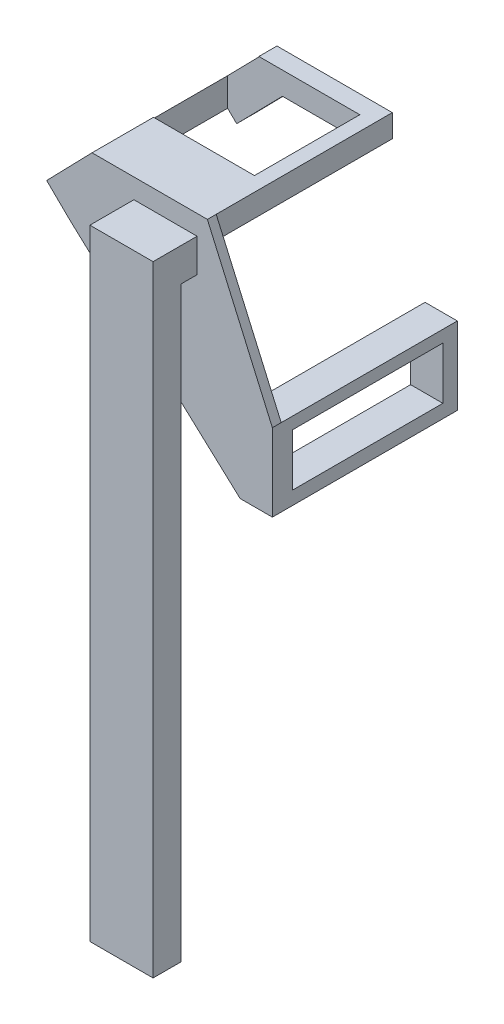
SolidWorks part; units mm, degrees
ref_plane "Front Plane" through (0, 0, 0) normal (0, 0, 1) x (1, 0, 0)
ref_plane "Top Plane" through (0, 0, 0) normal (0, 1, 0) x (1, 0, 0)
ref_plane "Right Plane" through (0, 0, 0) normal (1, 0, 0) x (0, 0, -1)
sketch "Sketch1" plane through (0, 0, 0) normal (0, 0, 1) x (1, 0, 0)
  line L0 (-37.3414, 34.6091) -> (22.6586, 34.6091)
  line L1 (22.6586, 34.6091) -> (50.9429, 6.3248)
  line L2 (50.9429, 6.3248) -> (50.9429, -53.6752)
  line L3 (50.9429, -53.6752) -> (22.6586, -81.9594)
  line L4 (22.6586, -81.9594) -> (-37.3414, -81.9594)
  line L5 (-37.3414, -81.9594) -> (-64.6578, -54.643)
  line L6 (-64.6578, -54.643) -> (-64.6578, 5.357)
  line L7 (-64.6578, 5.357) -> (-37.3414, 34.6091)
  line L8 (-27.6371, 26.0388) -> (-43.235, 10.1409)
  line L9 (33.6524, -24.3546) -> (22.6586, -24.3546)
  line L10 (33.6524, -24.3546) -> (33.6524, -50.7511)
  line L11 (33.6524, -50.7511) -> (22.6586, -50.7511)
  line L12 (22.6586, -24.3546) -> (22.6586, -50.7511)
  line L13 (28.1555, -50.7511) -> (28.1555, -24.3546) construction
  line L14 (33.6524, -37.5528) -> (22.6586, -37.5528) construction
  line L15 (-27.6371, 26.0388) -> (-19.7574, 18.3077)
  line L16 (-43.235, 10.1409) -> (-35.3553, 2.4098)
  line L17 (-19.7574, 18.3077) -> (-35.3553, 2.4098)
  line L19 (-27.7871, 26.0388) -> (11.5077, 26.0388)
  line L20 (-27.7871, 26.0388) -> (-27.7871, 18.3077)
  line L21 (-27.7871, 18.3077) -> (11.5077, 18.3077)
  line L22 (11.5077, 26.0388) -> (11.5077, 18.3077)
  line L23 (-8.1397, 18.3077) -> (-8.1397, 26.0388) construction
  line L24 (-27.7871, 22.1732) -> (11.5077, 22.1732) construction
  point P7 (28.1555, -37.5528)
  point P12 (-8.1397, 22.1732)
  dimension "D1" = 135
  dimension "D2" = 135
  dimension "D3" = 40
  dimension "D4" = 135
  dimension "D5" = 26.3965
  dimension "D6" = 10.9938
  dimension "D7" = 22.2719
  dimension "D8" = 11.039
  dimension "D9" = 7.7311
  dimension "D10" = 39.2948
extrude "Boss-Extrude1" add sketch "Sketch1" along normal blind 60 contours L21 L20 L8 L16 L17 | L9 L12 L11 L10 | L21 L22 L19 L20 region at (-32.4385, 13.235, 0) region at (28.1555, -37.5528, 0)
sketch "Sketch2" plane through (0, 0, 60) normal (0, 0, 1) x (1, 0, 0)
  line L0 (-43.235, 10.1409) -> (-27.7871, 26.0388)
  line L1 (-27.7871, 26.0388) -> (11.5077, 26.0388)
  line L2 (11.5077, 26.0388) -> (33.6524, -24.3546)
  line L3 (33.6524, -24.3546) -> (33.6524, -50.7511)
  line L4 (33.6524, -50.7511) -> (22.6586, -50.7511)
  line L5 (22.6586, -50.7511) -> (-35.3553, 2.4098)
  line L6 (-35.3553, 2.4098) -> (-43.235, 10.1409)
extrude "Boss-Extrude2" add sketch "Sketch2" along normal blind 3
sketch "Sketch3" plane through (0, 0, 63) normal (0, 0, 1) x (1, 0, 0)
  line L1 (-13.5192, 19.3171) -> (8.0096, 19.3171)
  line L2 (-13.5192, 19.3171) -> (-13.5192, 7.9709)
  line L3 (-13.5192, 7.9709) -> (8.0096, 7.9709)
  line L4 (8.0096, 19.3171) -> (8.0096, 7.9709)
  line L5 (-2.7548, 7.9709) -> (-2.7548, 19.3171) construction
  line L6 (-13.5192, 13.644) -> (8.0096, 13.644) construction
  point P0 (-2.7548, 13.644)
  dimension "D1" = 11.3463
  dimension "D2" = 21.5288
extrude "Boss-Extrude3" add sketch "Sketch3" along normal blind 15
sketch "Sketch4" plane through (0, 7.9709, 0) normal (0, -1, 0) x (1, 0, 0)
  line L1 (-13.5192, 78) -> (8.0096, 78)
  line L2 (-13.5192, 78) -> (-13.5192, 68.4327)
  line L3 (-13.5192, 68.4327) -> (8.0096, 68.4327)
  line L4 (8.0096, 78) -> (8.0096, 68.4327)
  line L5 (8.0096, 78) -> (8.0096, 63) construction
  dimension "D1" = 9.5673
  dimension "D2" = 21.5288
extrude "Boss-Extrude4" add sketch "Sketch4" along normal blind 200
sketch "Sketch5" plane through (22.6586, 0, 0) normal (-1, 0, 0) x (0, 0, 1)
  line L1 (4.9192, -28.4138) -> (56.2298, -28.4138)
  line L2 (4.9192, -28.4138) -> (4.9192, -46.1987)
  line L3 (4.9192, -46.1987) -> (56.2298, -46.1987)
  line L4 (56.2298, -28.4138) -> (56.2298, -46.1987)
  dimension "D1" = 17.785
  dimension "D2" = 51.3106
extrude "Cut-Extrude1" cut sketch "Sketch5" against normal blind 200
sketch "Sketch6" plane through (0, 26.0388, 0) normal (0, 1, 0) x (1, 0, 0)
  line L1 (6.5986, -6.1643) -> (-38.4315, -6.1643)
  line L2 (6.5986, -6.1643) -> (6.5986, -42.056)
  line L3 (6.5986, -42.056) -> (-38.4315, -42.056)
  line L4 (-38.4315, -6.1643) -> (-38.4315, -42.056)
  dimension "D1" = 35.8916
  dimension "D2" = 45.0301
extrude "Cut-Extrude2" cut sketch "Sketch6" against normal blind 200
